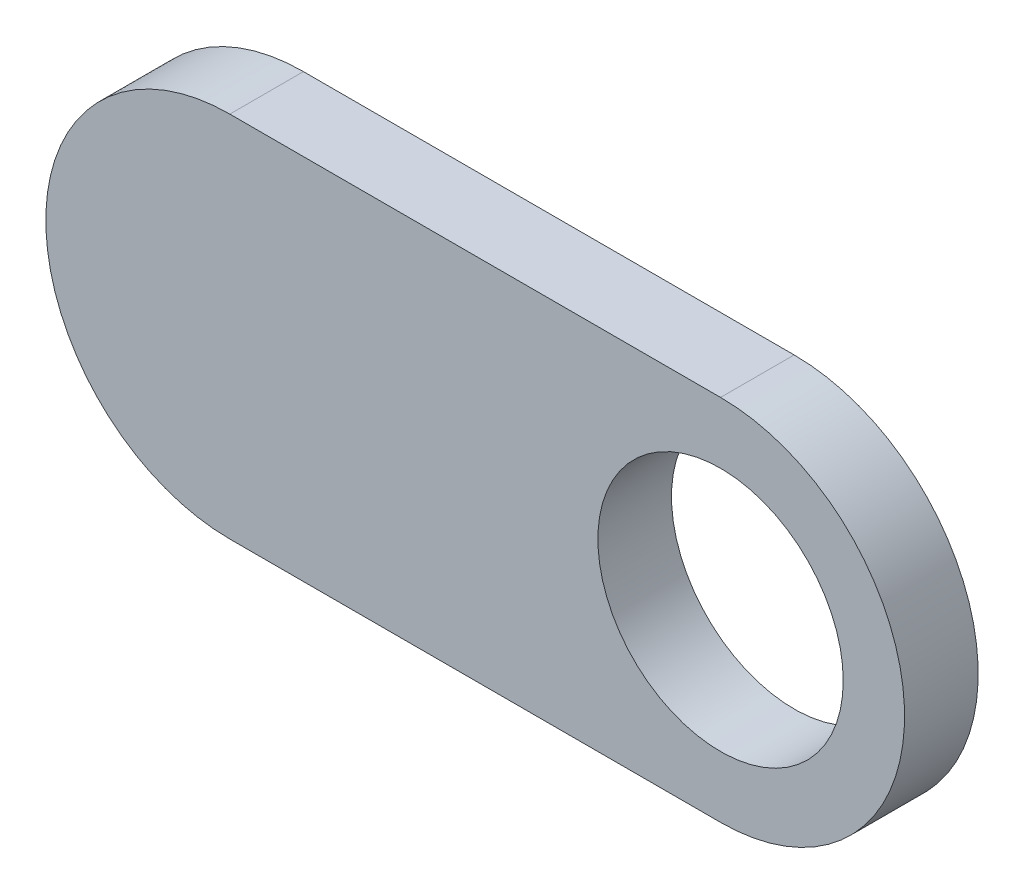
SolidWorks part; units mm, degrees
ref_plane "Front Plane" through (0, 0, 0) normal (0, 0, 1) x (1, 0, 0)
ref_plane "Top Plane" through (0, 0, 0) normal (0, 1, 0) x (1, 0, 0)
ref_plane "Right Plane" through (0, 0, 0) normal (1, 0, 0) x (0, 0, -1)
sketch "Sketch1" plane through (0, 0, 0) normal (0, 0, 1) x (1, 0, 0)
  line L0 (-10, 0) -> (10, 0) construction
  line L1 (-10, 7.5) -> (10, 7.5)
  line L2 (-10, -7.5) -> (10, -7.5)
  arc A2 (-10, 7.5) -> (-10, -7.5) centre (-10, 0) ccw
  arc A3 (10, -7.5) -> (10, 7.5) centre (10, 0) ccw
  circle A4 centre (10, 0) radius 5
  point P3 (0, 0)
  dimension "D1" = 7.5
  dimension "D2" = 20
  dimension "D3" = 10
base flange "Base-Flange1" sketch "Sketch1" thickness 3 reverse thickness direction no parameters "D1"=0.7366
sketch "Bend-Lines1" [suppressed] plane through (0, 0, 0) normal (0, 1, 0) x (1, 0, 0)
sketch "Bounding-Box1" [suppressed] plane through (0, 0, 0) normal (0, 1, 0) x (1, 0, 0)
sheet metal parameters "Sheet-Metal1" thickness 3 parameters "D1"=0.7366
flat pattern "Flat-Pattern1" [suppressed]
sketch "Bend-Lines2" plane through (0, 0, 0) normal (0, 1, 0) x (1, 0, 0)
sketch3d "Bounding-Box2" [suppressed]
  line L0 (-7.5, -7.5, 0) -> (27.5, -7.5, 0) construction
  line L1 (-7.5, 7.5, 0) -> (27.5, 7.5, 0) construction
  line L2 (-7.5, -7.5, 0) -> (-7.5, 7.5, 0) construction
  line L3 (27.5, -7.5, 0) -> (27.5, 7.5, 0) construction
